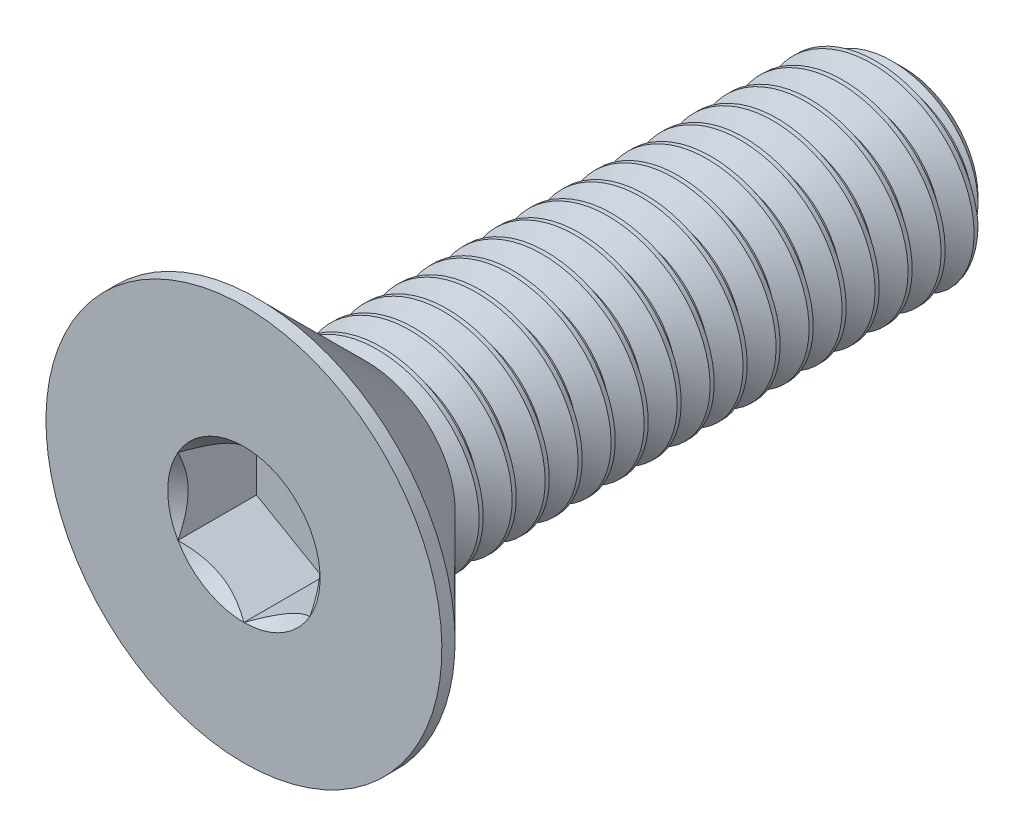
SolidWorks part; units mm, degrees
ref_plane "Front" through (0, 0, 0) normal (0, 0, 1) x (1, 0, 0)
ref_plane "Top" through (0, 0, 0) normal (0, 1, 0) x (1, 0, 0)
ref_plane "Right" through (0, 0, 0) normal (1, 0, 0) x (0, 0, -1)
sketch "Sketch1" plane through (0, 0, 0) normal (1, 0, 0) x (0, 0, -1)
  line L0 (0, 3) -> (0.2, 3) construction
  line L1 (0.2, 3) -> (1.7, 1.5) construction
  line L2 (0, 1.5) -> (10, 1.5)
  line L3 (10, 1.5) -> (10, 0)
  line L4 (10, 0) -> (0, 0)
  line L5 (0, 0) -> (0, 3) construction
  line L6 (0, 3) -> (0, -3) construction
  line L7 (10, 1.5) -> (10, -1.5) construction
  line L8 (0, -3) -> (0.2, -3) construction
  line L9 (0.2, -3) -> (1.7, -1.5) construction
  line L11 (0, 1.5) -> (0, 0)
  line L12 (1.7, 1.5) -> (1.7, 0) construction
revolve "Revolve1" add sketch "Sketch1" angle 360 mid plane about L4
sketch "Sketch3" plane through (0, 0, -10) normal (0, 0, -1) x (-1, 0, 0)
  circle A0 centre (0, 0) radius 1.5
curve "Helix/Spiral1" pitch 0.5 height 10 radius 1.5 centre (0, 0, -10) axis (0, 0, 1) start towards (0, 1, 0)
sketch "Sketch2" plane through (0, 0, 0) normal (1, 0, 0) x (0, 0, -1)
  line L0 (10, 1.5) -> (10.4375, 1.5)
  line L1 (10.4375, 1.5) -> (10.25, 1.1752)
  line L2 (10.25, 1.1752) -> (10.1875, 1.1752)
  line L3 (10.1875, 1.1752) -> (10, 1.5)
  line L4 (10.0938, 1.3376) -> (10.3437, 1.3376) construction
  dimension "D1" = 60
  dimension "D2" = 0.0625
  dimension "D3" = 0.25
chamfer "Chamfer1" distance 0.375 angle 45 1 edges at (0, 1.5, -10)
sweep "Cut-Sweep1" cut profiles "Sketch2" path "Helix/Spiral1" align with end faces yes
sketch "Sketch7" plane through (0, 0, 0) normal (1, 0, 0) x (0, 0, -1)
  line L0 (0, 3) -> (0.2, 3) construction
  line L1 (0.2, 3) -> (1.7, 1.5) construction
  line L2 (0, 3) -> (0.2, 3)
  line L3 (0.2, 3) -> (1.7, 1.5)
  line L4 (1.7, 1.5) -> (1.7, 0) construction
  line L5 (1.7, 1.5) -> (1.7, 0)
  line L7 (0, 0) -> (0, 3) construction
  line L8 (0, 0) -> (0, 3)
  line L9 (0, 0) -> (1.7, 0)
  line L10 (3.3, 0) -> (-3.3, 0) construction
revolve "Revolve2" add sketch "Sketch7" angle 360 mid plane about L9
ref_plane "Plane1" through (0, 0, -1.7) normal (0, 0, 1) x (1, 0, 0)
sketch "Sketch8" plane through (0, 0, -1.7) normal (0, 0, 1) x (1, 0, 0)
  circle A0 centre (0, 0) radius 1.5
extrude "Boss-Extrude1" add sketch "Sketch8" against normal through all draft 45
sketch "Sketch5" plane through (0, 0, 0) normal (0, 0, 1) x (1, 0, 0)
  line L1 (1, -0.5774) -> (1, 0.5774)
  line L2 (1, 0.5774) -> (0, 1.1547)
  line L3 (0, 1.1547) -> (-1, 0.5774)
  line L4 (-1, 0.5774) -> (-1, -0.5774)
  line L5 (-1, -0.5774) -> (0, -1.1547)
  line L6 (0, -1.1547) -> (1, -0.5774)
  circle A0 centre (0, 0) radius 1 construction
  dimension "Hex" = 2
extrude "Cut-Extrude2" cut sketch "Sketch5" against normal blind 1.19
sketch "Sketch6" plane through (0, 0, 0) normal (0, 0, 1) x (1, 0, 0)
  circle A0 centre (0, 0) radius 1.1547
extrude "Cut-Extrude3" cut sketch "Sketch6" against normal blind 1.19 draft 45
sketch "Sketch9" [suppressed] plane through (0, 0, -5.5) normal (0, 0, 1) x (1, 0, 0)
  circle A1 centre (0, 0) radius 5
  circle A2 centre (0, 0) radius 5
  point P0 (0, 5)
  dimension "D1" = 0
extrude "Boss-Extrude2" [suppressed] add sketch "Sketch9" against normal offset from surface (18.5 mm away) 26 up to face at (0, 1.125, -10)
fillet "Fillet1" [suppressed] radius 0.3
sketch "Sketch10" plane through (0, 0, 0) normal (1, 0, 0) x (0, 0, -1)
  line L0 (10, 1.5) -> (10, -1.5) construction
  point P0 (9.25, -1.5)
  dimension "D1" = 0.75
equation "\"D3@Helix/Spiral1\" = \"Lg@Sketch1\""
equation "\"D2@Sketch2\" = \"D4@Helix/Spiral1\" * .125"
equation "\"D3@Sketch2\" = \"D4@Helix/Spiral1\" * .5"
equation "\"D1@Chamfer1\" = \"D4@Helix/Spiral1\" * .75"
equation "\"D1@Cut-Extrude2\" = \"Head Ht@Sketch1\" * .7"
equation "\"D1@Sketch10\" = \"D4@Helix/Spiral1\" * 1.5"
equation "\"D1@Cut-Extrude3\" = \"D1@Cut-Extrude2\""
equation "\"D1@Fillet1\" = \"Dia@Sketch1\" * .1"
